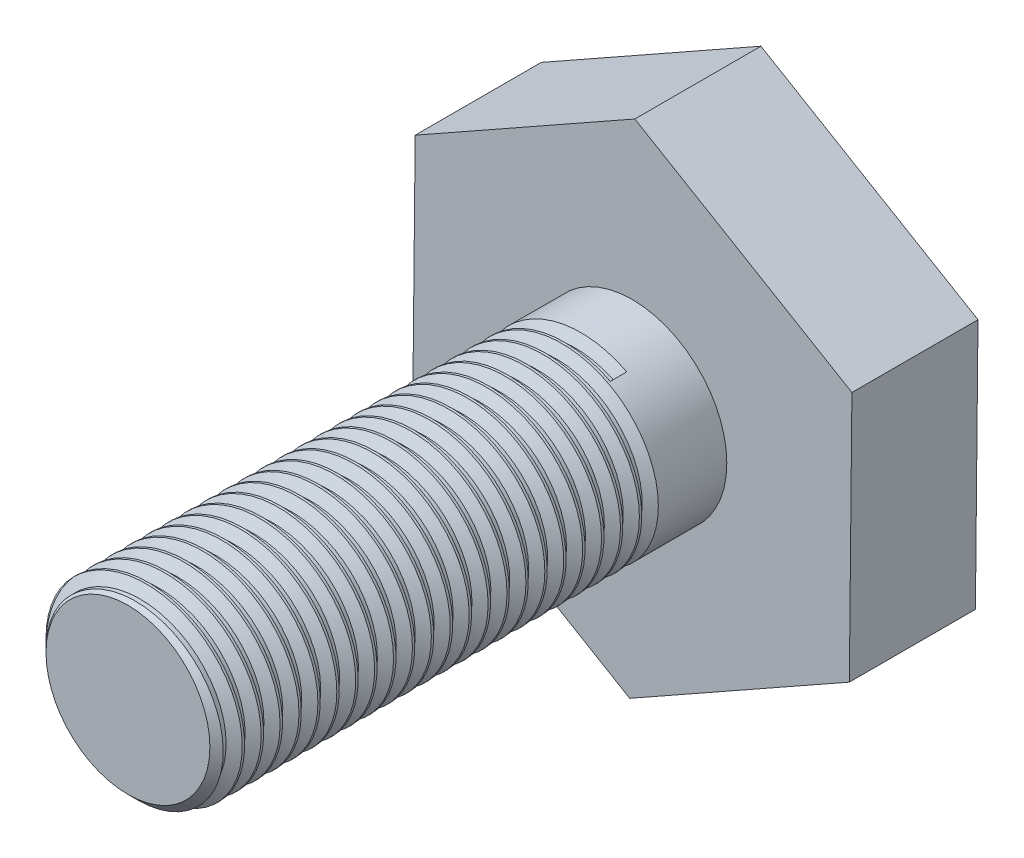
SolidWorks part; units mm, degrees
ref_plane "Front Plane" through (0, 0, 0) normal (0, 0, 1) x (1, 0, 0)
ref_plane "Top Plane" through (0, 0, 0) normal (0, 1, 0) x (1, 0, 0)
ref_plane "Right Plane" through (0, 0, 0) normal (1, 0, 0) x (0, 0, -1)
sketch "Sketch1" plane through (0, 0, 0) normal (0, 0, 1) x (1, 0, 0)
  line L1 (17.2183, -10.177) -> (17.4227, 9.823)
  line L2 (17.4227, 9.823) -> (0.2043, 20)
  line L3 (0.2043, 20) -> (-17.2183, 10.177)
  line L4 (-17.2183, 10.177) -> (-17.4227, -9.823)
  line L5 (-17.4227, -9.823) -> (-0.2043, -20)
  line L6 (-0.2043, -20) -> (17.2183, -10.177)
  circle A0 centre (0, 0) radius 17.3214 construction
  point P11 (2.3655, -26.9002)
  point P12 (-12.2674, -15.0179)
  dimension "D1" = 20
  dimension "D2" = 34.6428
extrude "Boss-Extrude1" add sketch "Sketch1" along normal blind 10
sketch "Sketch2" plane through (0, 0, 10) normal (0, 0, 1) x (1, 0, 0)
  circle A0 centre (0, 0) radius 7.5
  dimension "D1" = 15
extrude "Boss-Extrude2" add sketch "Sketch2" along normal blind 40
chamfer "Chamfer1" distance 1 angle 45 1 edges at (7.5, 0, 50)
thread "Thread1" pitch 1.5 method cut profile "Thread Profile1" start angle 0, offset 1.5, length 35, pitch 1.5, diameter 15
ref_plane "Plane1" through (-7.5, 0, 50.5) normal (0, -1, 0) x (-1, 0, 0)
sketch "Thread Profile1" plane through (-7.5, 0, 50.5) normal (0, -1, 0) x (-1, 0, 0)
  line L0 (0, 0) -> (0, 1.5) construction
  line L11 (0, 0) -> (0, 1.3125)
  line L12 (0, 1.3125) -> (-0.8119, 0.8437)
  line L13 (-0.8119, 0.8437) -> (-0.8119, 0.4687)
  line L15 (-0.8119, 0.4687) -> (0, 0)
  line L17 (-0.8119, 0.6562) -> (0, 0.6562) construction
  point P2 (0, 0)
  dimension "Pitch" = 1.5
  dimension "Profile_Angle" = 60
  dimension "Profile_Land" = 0.375
  dimension "Profile_Height" = 0.8119
sketch "Sketch8" plane through (0, 0, 0) normal (-0.866, 0.5, 0) x (0, 0, 1)
  line L1 (14.1868, 7.5) -> (15.4993, 7.5) construction
  line L2 (14.5606, 7.5) -> (15.1254, 7.5)
  arc A1 (14.5606, 7.5) -> (15.1254, 7.5) centre (14.843, 7.5) ccw
  dimension "D1" = 0.2824
extrude "Cut-Extrude1" [suppressed] cut sketch "Sketch8" against normal blind 40
